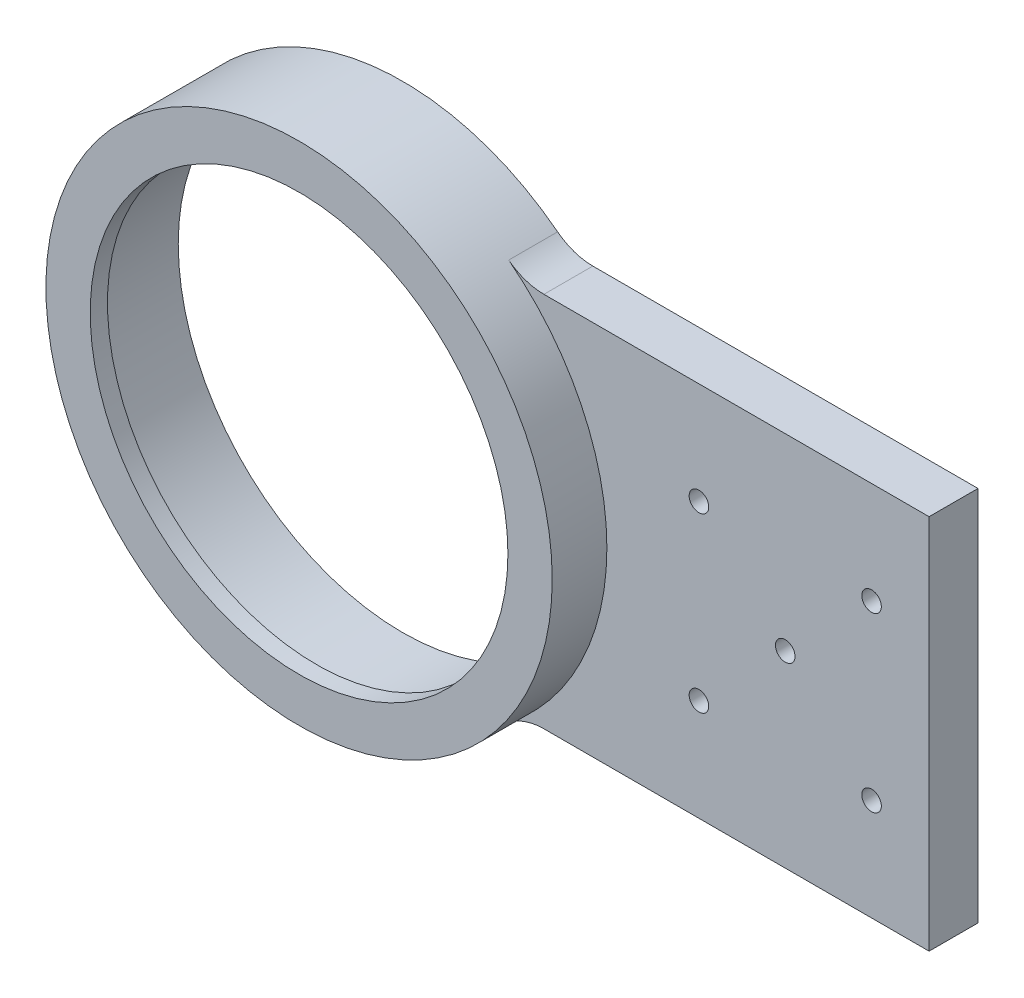
SolidWorks part; units mm, degrees
material "ABS"
ref_plane "Front" through (0, 0, 0) normal (0, 0, 1) x (1, 0, 0)
ref_plane "Top" through (0, 0, 0) normal (0, 1, 0) x (1, 0, 0)
ref_plane "Right" through (0, 0, 0) normal (1, 0, 0) x (0, 0, -1)
sketch "Croquis1" plane through (0, 0, 0) normal (0, 0, 1) x (1, 0, 0)
  circle A0 centre (0, 0) radius 36.3
  circle A1 centre (0, 0) radius 44
  dimension "D1" = 72.6
  dimension "D2" = 88
extrude "Saliente-Extruir1" add sketch "Croquis1" along normal blind 3
sketch "Croquis2" plane through (0, 0, 0) normal (0, 0, -1) x (-1, 0, 0)
  circle A0 centre (0, 0) radius 39
  circle A1 centre (0, 0) radius 44 construction
  circle A2 centre (0, 0) radius 44
  dimension "D1" = 78
extrude "Saliente-Extruir2" add sketch "Croquis2" along normal blind 15
sketch "Croquis3" plane through (0, 0, -15) normal (0, 0, -1) x (-1, 0, 0)
  line L0 (-29.4399, 32.7) -> (-100, 32.7)
  line L1 (-100, 32.7) -> (-100, -32.7)
  line L2 (-100, -32.7) -> (-29.4399, -32.7)
  line L3 (10.5108, 0) -> (-10.5108, 0) construction
  line L4 (0, 10.5108) -> (0, -10.5108) construction
  circle A0 centre (0, 0) radius 44 construction
  arc A1 (-29.4399, 32.7) -> (-29.4399, -32.7) centre (0, 0) ccw
  point P9 (-100, 0)
  dimension "D1" = 65.4
  dimension "D2" = 100
extrude "Saliente-Extruir3" add sketch "Croquis3" against normal blind 8.5
fillet "Redondeo1" radius 10 2 edges at (29.4399, -32.7, -10.75) (29.4399, 32.7, -10.75)
hole_wizard "Taladro de margen para M31" positions "Croquis4" profile "Croquis5" hole size "M3" standard "Ansi Metric" end condition up to next
sketch "Croquis4" plane through (0, 0, -15) normal (0, 0, -1) x (-1, 0, 0)
  line L1 (-60, -15) -> (-90, -15) construction
  line L2 (-60, -15) -> (-60, 15) construction
  line L3 (-60, 15) -> (-90, 15) construction
  line L4 (-90, -15) -> (-90, 15) construction
  line L5 (-60, -15) -> (-90, 15) construction
  line L6 (-60, 15) -> (-90, -15) construction
  line L7 (9.9, 0) -> (-9.9, 0) construction
  line L8 (-100, 32.7) -> (-100, -32.7) construction
  point P1 (-75, 0)
  point P2 (-90, 15)
  point P35 (-60, -15)
  point P36 (-60, 15)
  point P37 (-90, -15)
  dimension "D1" = 30
  dimension "D2" = 25
sketch "Croquis5" plane through (75, 0, -15) normal (1, 0, 0) x (0, 1, 0)
  line L0 (0, 0) -> (0, 8.5)
  line L1 (0, 8.5) -> (1.7, 8.5)
  line L2 (1.7, 8.5) -> (1.7, 0)
  line L5 (1.7, 0) -> (0, 0)
  line L11 (0, -6.35) -> (0, 107.95) construction
  dimension "Diámetro de taladro hasta el siguiente" = 3.4
  dimension "Profundidad de taladro hasta el siguiente" = 8.5
